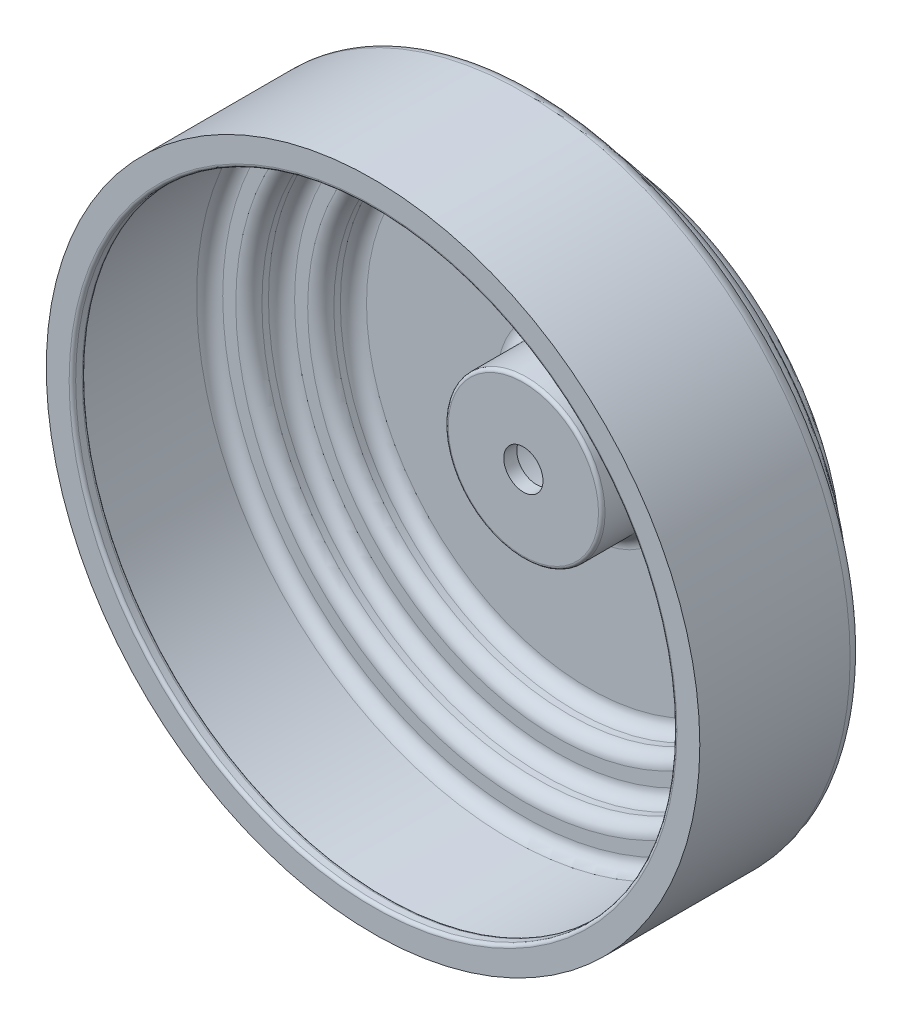
SolidWorks part; units mm, degrees
material "A356-T6 cast aluminum alloy"
ref_plane "Front Plane" through (0, 0, 0) normal (1, 0, 0) x (0, 1, 0)
ref_plane "Top Plane" through (0, 0, 0) normal (0, 0, 1) x (0, 1, 0)
ref_plane "Right Plane" through (0, 0, 0) normal (0, 1, 0) x (-1, 0, 0)
sketch "Sketch1" plane through (0, 0, 0) normal (1, 0, 0) x (0, 1, 0)
  line L0 (0, 39.2665) -> (0, -43.352) construction
  line L1 (-64.066, 0) -> (74.2367, 0) construction
  line L2 (-50, 35) -> (-50, 10)
  line L3 (-46, 35) -> (-46, 33)
  line L4 (-50, 10) -> (-44, 10)
  line L5 (-44, 10) -> (-44, 5)
  line L6 (-44, 5) -> (-38, 5)
  line L7 (-38, 5) -> (-38, 0)
  line L8 (-38, 0) -> (-10, 0)
  line L9 (-10, 0) -> (-10, 10)
  line L10 (-10, 10) -> (-3, 10)
  line L11 (-50, 35) -> (-46, 35)
  line L12 (-48, 33) -> (-48, 12)
  line L13 (-48, 12) -> (-42, 12)
  line L14 (-42, 12) -> (-42, 7)
  line L15 (-42, 7) -> (-36, 7)
  line L16 (-36, 7) -> (-36, 2)
  line L17 (-36, 2) -> (-12, 2)
  line L18 (-46, 33) -> (-48, 33)
  line L19 (-12, 2) -> (-12, 12)
  line L20 (-48, 35) -> (-48, 12) construction
  line L21 (-12, 12) -> (-3, 12)
  line L22 (-3, 12) -> (-3, 10)
  line L23 (-12, 0) -> (-12, 12) construction
  line L24 (-36, 2) -> (-10, 2) construction
  line L26 (-10, 10) -> (0, 10) construction
  line L27 (-12, 12) -> (0, 12) construction
  point P10 (-38, 2.5)
  dimension "D1" = 35
  dimension "D2" = 100
  dimension "D3" = 92
  dimension "D4" = 25
  dimension "D5" = 20
  dimension "D6" = 38
  dimension "D7" = 5
  dimension "D8" = 6
  dimension "D9" = 2
  dimension "D12" = 6
  dimension "D13" = 10
  dimension "D10" = 2
  dimension "D11" = 2
revolve "Revolve1" add sketch "Sketch1" angle 360 about L0
fillet "Fillet1" radius 2 11 edges at (50, 0, 10) (44, 0, 10) (44, 0, 5) (38, 0, 5) (38, 0, 0) (48, 0, 12) (42, 0, 12) (42, 0, 7) (36, 0, 7) (36, 0, 2) (12, 0, 2)
fillet "Fillet2" radius 0.5 4 edges at (12, 0, 12) (46, 0, 35) (46, 0, 33) (10, 0, 0)
ref_axis "Axis1" through (0, 0, -1.75) along (0, 0, 1)
